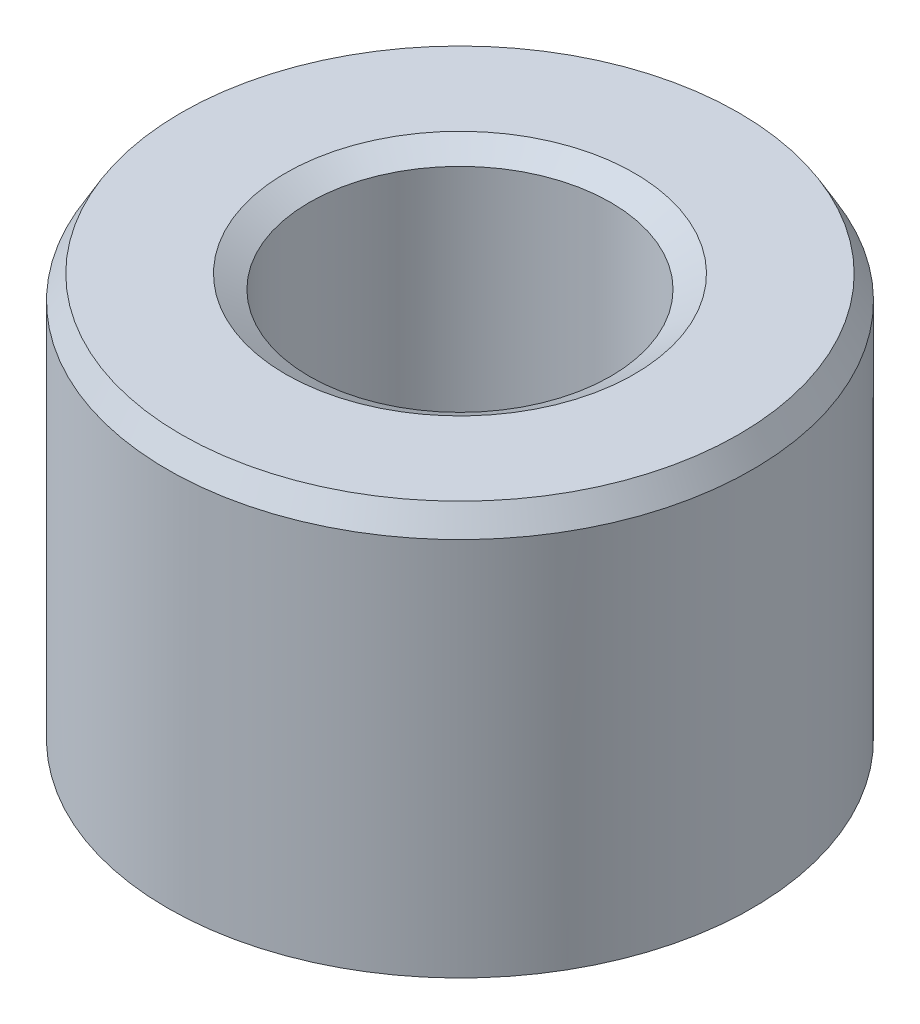
SolidWorks part; units mm, degrees
ref_plane "Front Plane" through (0, 0, 0) normal (0, 0, 1) x (1, 0, 0)
ref_plane "Top Plane" through (0, 0, 0) normal (0, 1, 0) x (1, 0, 0)
ref_plane "Right Plane" through (0, 0, 0) normal (1, 0, 0) x (0, 0, -1)
sketch "Sketch1" plane through (0, 0, 0) normal (0, 1, 0) x (1, 0, 0)
  circle A0 centre (0, 0) radius 10
  dimension "SLEEVE_OD" = 20
extrude "Boss-Extrude1" add sketch "Sketch1" along normal blind 14.2593
sketch "Sketch2" plane through (0, 0, 0) normal (0, 1, 0) x (1, 0, 0)
  circle A0 centre (0, 0) radius 5.1534
  dimension "BORE_D" = 10.3067
extrude "Cut-Extrude1" cut sketch "Sketch2" along normal through all
chamfer "Chamfer1" distance 0.8084 angle 30 4 edges at (0, 14.2593, 5.1534) (0, 0, 5.1534) (0, 0, 10) (0, 14.2593, 10) first distance on face at (0, 14.2593, 5.1534) first distance on face at (0, 0, 5.1534) first distance on face at (0, 14.2593, 10)
